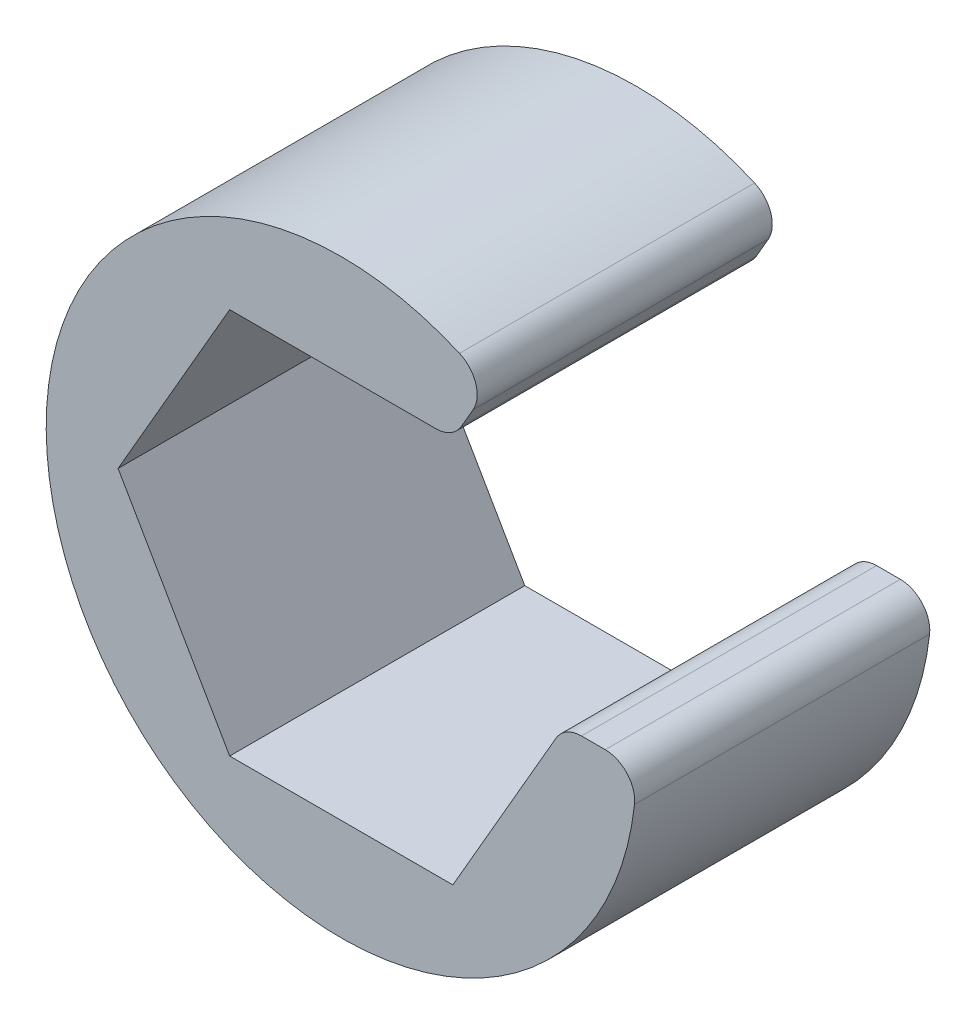
SolidWorks part; units mm, degrees
ref_plane "Front Plane" through (0, 0, 0) normal (0, 0, 1) x (1, 0, 0)
ref_plane "Top Plane" through (0, 0, 0) normal (0, 1, 0) x (1, 0, 0)
ref_plane "Right Plane" through (0, 0, 0) normal (1, 0, 0) x (0, 0, -1)
sketch "Sketch1" plane through (0, 0, 0) normal (0, 0, 1) x (1, 0, 0)
  line L0 (5, 8.6603) -> (3.7816, 6.55)
  line L2 (3.7816, 6.55) -> (-3.7816, 6.55)
  line L3 (-3.7816, 6.55) -> (-7.5633, 0)
  line L4 (-7.5633, 0) -> (-3.7816, -6.55)
  line L5 (-3.7816, -6.55) -> (3.7816, -6.55)
  line L6 (3.7816, -6.55) -> (7.5633, 0)
  line L7 (10, 0) -> (7.5633, 0)
  line L9 (7.5633, 0) -> (5.6725, 3.275) [skipped]
  circle A0 centre (0, 0) radius 6.55 construction
  arc A1 (5, 8.6603) -> (10, 0) centre (0, 0) ccw
  point P1 (0, 0)
  point P12 (14.6926, -0.3674)
  point P15 (0, 0)
  dimension "D1" = 13.1
  dimension "D4" = 20
  dimension "D2" = 120
  dimension "D3" = 120
extrude "Boss-Extrude1" add sketch "Sketch1" along normal blind 10 contours A1 L7 L6 L5 L4 L3 L2 L0
fillet "Fillet1" radius 1 4 edges at (7.5633, 0, 5) (10, 0, 5) (3.7816, 6.55, 5) (5, 8.6603, 5)
